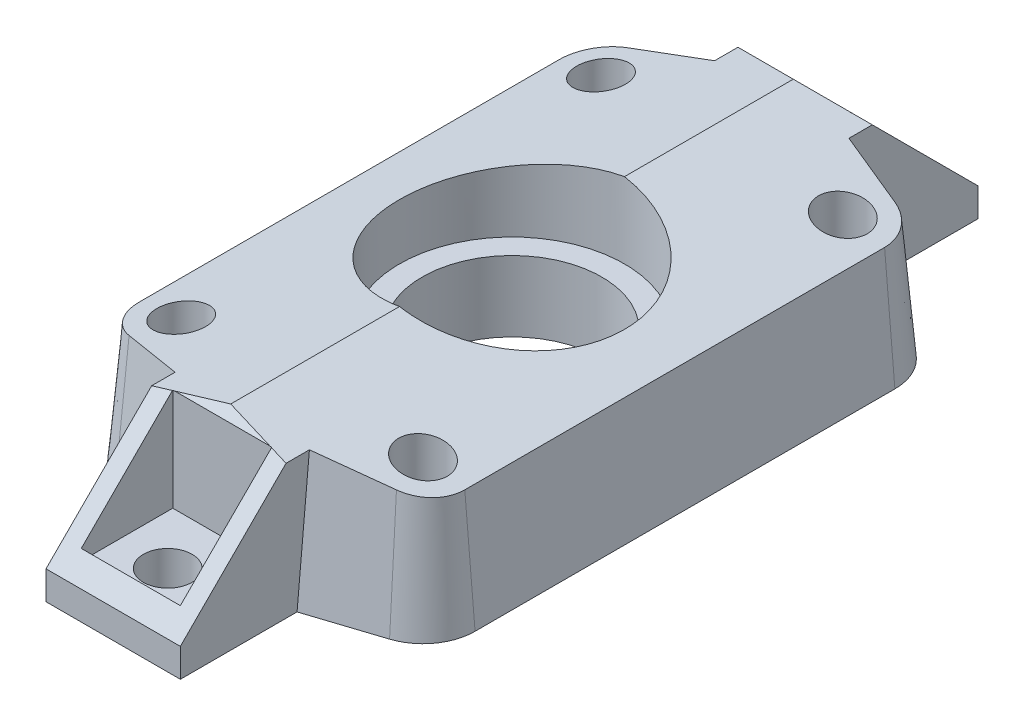
SolidWorks part; units mm, degrees
ref_plane "Front Plane" through (0, 0, 0) normal (0, 0, 1) x (1, 0, 0)
ref_plane "Top Plane" through (0, 0, 0) normal (0, 1, 0) x (1, 0, 0)
ref_plane "Right Plane" through (0, 0, 0) normal (1, 0, 0) x (0, 0, -1)
sketch "Sketch1" plane through (0, 0, 0) normal (0, 1, 0) x (1, 0, 0)
  line L0 (-50.5514, 53.977) -> (-30.2314, 53.977)
  line L1 (-30.2314, 53.977) -> (-30.2314, 36.3221)
  line L2 (-30.2314, 36.3221) -> (-19.6702, 32.8906)
  line L3 (-14.2294, 25.402) -> (-14.2294, -38.098)
  line L4 (-19.6702, -45.5866) -> (-30.2314, -49.0182)
  line L5 (-30.2314, -49.0182) -> (-30.2314, -66.673)
  line L6 (-30.2314, -66.673) -> (-50.5514, -66.673)
  line L7 (-50.5514, -66.673) -> (-50.5514, -49.0182)
  line L8 (-50.5514, -49.0182) -> (-61.1126, -45.5866)
  line L9 (-66.5534, -38.098) -> (-66.5534, 25.402)
  line L10 (-50.5514, 36.3221) -> (-50.5514, 53.977)
  line L11 (-61.1126, 32.8906) -> (-50.5514, 36.3221)
  line L12 (-40.3914, 53.977) -> (-40.3914, -66.673) construction
  line L14 (-32.8984, 51.31) -> (-47.8844, 51.31)
  line L15 (-32.8984, 51.31) -> (-32.8984, 37.467)
  line L16 (-32.8984, 37.467) -> (-47.8844, 37.467)
  line L17 (-47.8844, 51.31) -> (-47.8844, 37.467)
  line L18 (-32.8984, -50.163) -> (-47.8844, -50.163)
  line L19 (-32.8984, -50.163) -> (-32.8984, -64.006)
  line L20 (-32.8984, -64.006) -> (-47.8844, -64.006)
  line L21 (-47.8844, -50.163) -> (-47.8844, -64.006)
  arc A0 (-66.5534, 25.402) -> (-61.1126, 32.8906) centre (-58.6794, 25.402) cw
  arc A1 (-61.1126, -45.5866) -> (-66.5534, -38.098) centre (-58.6794, -38.098) cw
  arc A2 (-14.2294, -38.098) -> (-19.6702, -45.5866) centre (-22.1034, -38.098) cw
  arc A3 (-19.6702, 32.8906) -> (-14.2294, 25.402) centre (-22.1034, 25.402) cw
  circle A5 centre (-40.3914, -6.348) radius 17.018
  circle A6 centre (-40.3914, -6.348) radius 13.589
  circle A8 centre (-40.3914, 45.722) radius 3.683
  circle A9 centre (-40.3914, -58.418) radius 3.683
  circle A10 centre (-22.1034, 25.402) radius 3.683
  circle A11 centre (-58.6794, 25.402) radius 3.683
  circle A12 centre (-58.6794, -38.098) radius 3.683
  circle A13 centre (-22.1034, -38.098) radius 3.683
  point P14 (-66.5534, 31.1228)
  point P17 (-66.5534, -43.8188)
  point P24 (-40.3914, -66.673)
  point P40 (-40.3914, 37.467)
  point P45 (-40.3914, -50.163)
  dimension "D7" = 7.874
  dimension "D8" = 7.874
  dimension "D9" = 63.5
  dimension "D11" = 34.036
  dimension "D12" = 27.178
  dimension "D13" = 7.366
  dimension "D14" = 14.986
  dimension "D1" = 108
  dimension "D2" = 108
  dimension "D3" = 108
  dimension "D4" = 108
  dimension "D5" = 8.128
  dimension "D6" = 20.32
  dimension "D10" = 120.65
  dimension "D15" = 52.07
  dimension "D16" = 104.14
  dimension "D17" = 2.667
  dimension "D18" = 2.667
  dimension "D19" = 87.63
extrude "Boss-Extrude2" add sketch "Sketch1" along normal blind 22.098 contours L12 L0 L10 L11 A0 L9 A1 L8 L7 L6 A5 | L0 L12 A5 L6 L5 L4 A2 L3 A3 L2 L1 region at (-40.3914, 0, -52.6619)
draft "Draft2" type of draft neutral plane draft angle 5 faces to draft 10 face at (-55.832, 11.049, -34.6064) face at (-64.4413, 11.049, -29.5882) face at (-66.5534, 11.049, 6.348) face at (-64.4413, 11.049, 42.2843) face at (-55.832, 11.049, 47.3024) face at (-16.3415, 11.049, 42.2843) face at (-24.9508, 11.049, 47.3024) face at (-24.9508, 11.049, -34.6064) face at (-16.3415, 11.049, -29.5882) face at (-14.2294, 11.049, 6.348) neutral plane through (0, 0, 0) neutral plane normal (0, -1, 0) reverse direction yes parameters "D1"=5
extrude "Boss-Extrude3" add sketch "Sketch1<4>" along normal blind 5.334 contours L12 L18 L21 L20 A9 | L18 L12 A9 L20 L19 | L12 L14 L17 L16 A8 | L14 L12 A8 L16 L15 region at (-36.0804, 0, -44.0437) region at (-44.7023, 0, -44.0437) region at (-36.0804, 0, 56.7398) region at (-44.7023, 0, 56.7398)
sketch "Sketch1<4>" plane through (0, 0, 0) normal (0, 1, 0) x (1, 0, 0) same geometry as "Sketch1"
sketch "Sketch2" plane through (0, 0, 0) normal (1, 0, 0) x (0, 0, -1)
  line L0 (-48.893, 22.098) -> (-81.2575, -10.2665) construction
  line L1 (-46.9854, 22.098) -> (-66.673, 22.098) construction
  line L2 (-48.893, 22.098) -> (36.197, 22.098) construction
  line L3 (53.977, 22.098) -> (34.2893, 22.098) construction
  line L4 (36.197, 22.098) -> (68.4635, -10.1685) construction
  line L5 (-66.673, 22.098) -> (53.977, 22.098) construction
  line L6 (53.977, 22.098) -> (53.977, 0) construction
  line L7 (-66.673, 4.318) -> (-66.673, 22.098)
  line L8 (-66.673, 22.098) -> (-66.673, 0) construction
  line L9 (-66.673, 22.098) -> (-48.893, 22.098)
  line L10 (-48.893, 22.098) -> (-66.673, 4.318)
  line L11 (36.197, 22.098) -> (53.977, 22.098)
  line L12 (53.977, 4.318) -> (53.977, 22.098)
  line L13 (36.197, 22.098) -> (53.977, 4.318)
  line L14 (-66.673, 0) -> (53.977, 0) construction
  point P16 (-6.348, 22.098)
  dimension "D1" = 45
  dimension "D2" = 45
  dimension "D3" = 4.318
extrude "Cut-Extrude1" cut sketch "Sketch2" against normal through all both and the other way through all
sketch "Sketch3" plane through (0, 0, 0) normal (0, 0, 1) x (1, 0, 0)
  line L0 (-40.3914, 22.098) -> (-40.3914, 0) construction
  line L1 (-30.2314, 22.098) -> (-50.5514, 22.098) construction
  line L2 (-30.2314, 0) -> (-50.5514, 0) construction
  line L3 (-40.3914, 22.098) -> (-2.8232, 15.4737) construction
  line L4 (-40.3914, 22.098) -> (-77.9595, 15.4737) construction
  line L5 (-73.749, 22.098) -> (-9.577, 22.098) construction
  line L6 (-64.62, 22.098) -> (-16.1627, 22.098)
  line L7 (-40.3914, 22.098) -> (-64.9997, 17.7589)
  line L8 (-64.62, 22.098) -> (-66.5534, 0) construction
  line L9 (-40.3914, 22.098) -> (-15.7831, 17.7589)
  line L10 (-64.9997, 17.7589) -> (-64.62, 22.098)
  line L11 (-15.7831, 17.7589) -> (-16.1627, 22.098)
  line L12 (-64.62, 22.098) -> (-66.5534, 0) construction
  line L13 (-16.1627, 22.098) -> (-14.2294, 0) construction
  dimension "D1" = 10
  dimension "D2" = 10
extrude "Cut-Extrude2" cut sketch "Sketch3" against normal through all both and the other way through all contours L10 L7 L6 | L9 L11 L6 region at (-24.1124, 20.6516, 0) region at (-56.6704, 20.6516, 0)
extrude "Boss-Extrude4" add sketch "Sketch1<5>" along normal blind 10.668 contours L12 A5 A6 | A5 L12 A6 region at (-28.6269, 0, -5.4164) region at (-40.7719, 0, -8.9555)
sketch "Sketch1<5>" plane through (0, 0, 0) normal (0, 1, 0) x (1, 0, 0) same geometry as "Sketch1"
